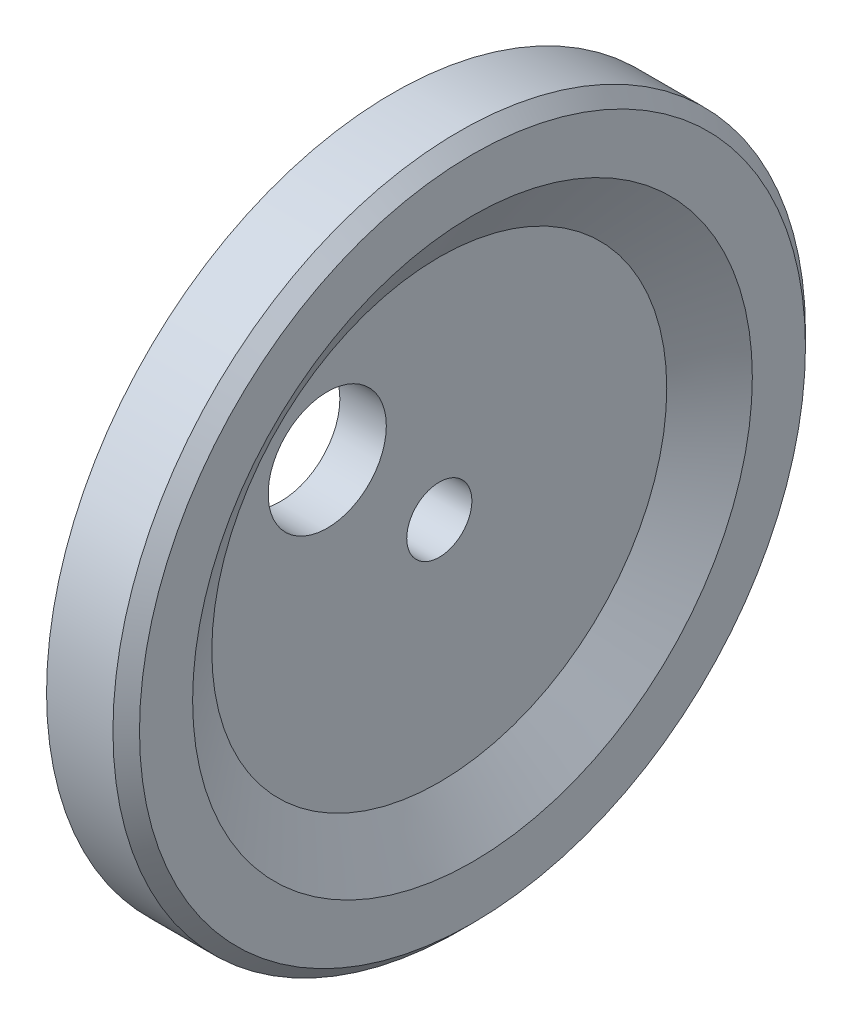
SolidWorks part; units mm, degrees
ref_plane "Front Plane" through (0, 0, 0) normal (0, 0, 1) x (1, 0, 0)
ref_plane "Top Plane" through (0, 0, 0) normal (0, 1, 0) x (1, 0, 0)
ref_plane "Right Plane" through (0, 0, 0) normal (1, 0, 0) x (0, 0, -1)
sketch "Sketch1" plane through (0, 0, 0) normal (0, 1, 0) x (1, 0, 0)
  line L1 (0, -55) -> (0, 55) construction
  line L2 (0, 4.9022) -> (0, 52.15)
  line L3 (0, 52.15) -> (12, 52.15)
  line L4 (12, 52.15) -> (12, 42.15)
  line L8 (7, 4.9022) -> (7, 34.26)
  line L9 (7, 34.26) -> (12, 42.15)
  line L10 (0, 4.9022) -> (7, 4.9022)
  dimension "D2" = 47.2478
  dimension "D3" = 12
  dimension "D4" = 10
  dimension "D6" = 29.3578
sketch "Sketch2" plane through (0, 0, 0) normal (0, 1, 0) x (1, 0, 0)
  line L0 (0, 0) -> (9.8109, 0)
  line L1 (-5.5, 0) -> (5.5, 0) construction
revolve "Revolve1" add sketch "Sketch1" angle 360 about L0
chamfer "Chamfer1" distance 2 angle 45 1 edges at (12, 0, 52.15)
sketch "Sketch3" plane through (7, 0, 0) normal (1, 0, 0) x (0, 0, -1)
  circle A0 centre (-16.8752, 16.2253) radius 8.9
extrude "Cut-Extrude1" cut sketch "Sketch3" against normal blind 10
